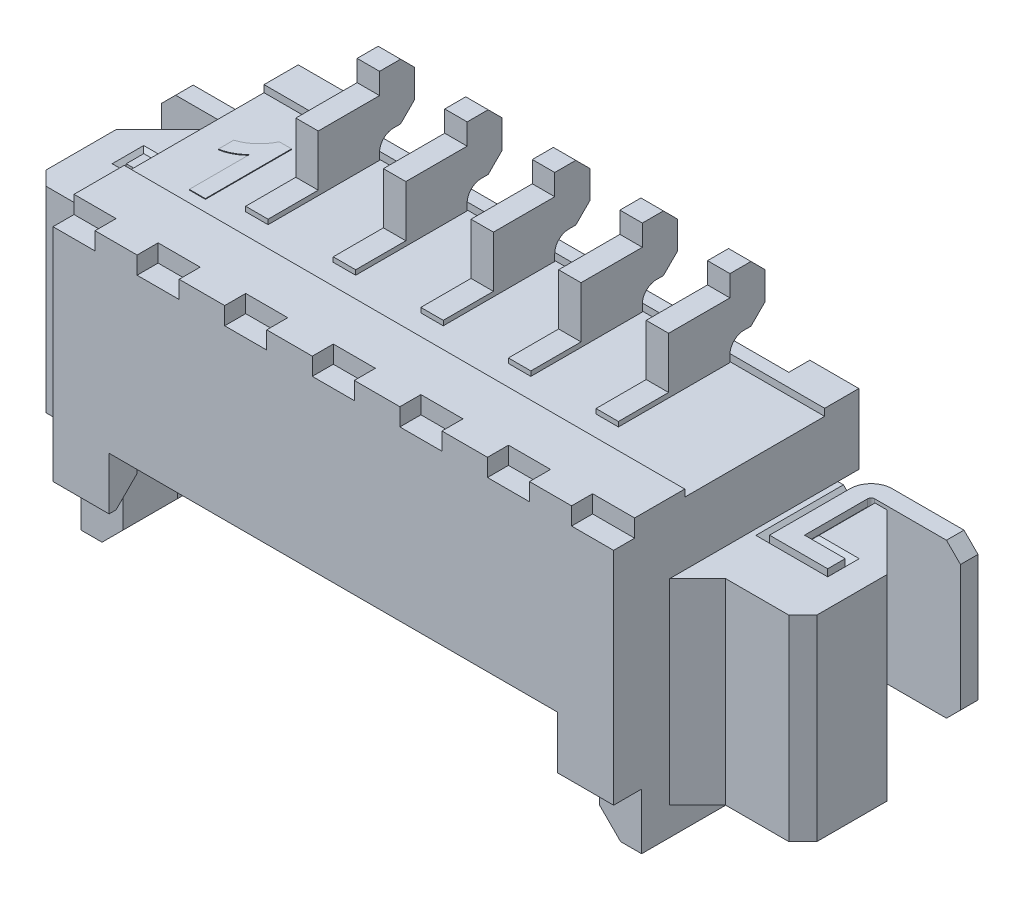
SolidWorks part; units mm, degrees
ref_plane "Спереди" through (0, 0, 0) normal (0, 0, 1) x (1, 0, 0)
ref_plane "Сверху" through (0, 0, 0) normal (0, 1, 0) x (1, 0, 0)
ref_plane "Справа" through (0, 0, 0) normal (1, 0, 0) x (0, 0, -1)
sketch "Эскиз1" plane through (0, 0, 0) normal (0, 1, 0) x (1, 0, 0)
  line L0 (3.4, -1.5) -> (3.4, -0.7)
  line L1 (-4, -0.3) -> (-4, -3.1)
  line L2 (3.7, -1.5) -> (3.4, -1.5)
  line L3 (-3.7, -2.325) -> (-3.7, -1.5)
  line L4 (-4, -3.1) -> (-3.4, -3.1)
  line L5 (-3.7, -2.325) -> (-3.4, -2.325)
  line L6 (-3.4, -2.325) -> (-3.4, -3.1)
  line L7 (3.4, -2.325) -> (3.4, -3.1)
  line L8 (3.7, -2.325) -> (3.4, -2.325)
  line L9 (0, -1.9) -> (0, -3.3692) construction
  line L10 (-3.7, -1.5) -> (-3.4, -1.5)
  line L11 (-3.4, -1.5) -> (-3.4, -0.7)
  line L12 (4, -3.1) -> (3.4, -3.1)
  line L13 (3.7, -2.325) -> (3.7, -1.5)
  line L14 (4, -0.3) -> (4, -3.1)
  line L15 (-4, -0.3) -> (4, -0.3)
  line L16 (3.4, -0.7) -> (-3.4, -0.7)
  dimension "D1" = 0.6
  dimension "D2" = 0.3
  dimension "D3" = 0.3
  dimension "D4" = 2.8
  dimension "D5" = 4
extrude "Вытянуть1" add sketch "Эскиз1" against normal blind 4.2
sketch "Эскиз2" plane through (0, 0, 0) normal (0, 1, 0) x (1, 0, 0)
  line L0 (-4, -3.1) -> (-3.4, -3.1)
  line L1 (-3.4, -3.1) -> (-3.4, -3.5)
  line L2 (-4, -3.1) -> (-4, -3.5)
  line L3 (-4, -3.5) -> (-3.4, -3.5)
  line L4 (0, -2.1744) -> (0, -2.7597) construction
  line L5 (4, -3.5) -> (3.4, -3.5)
  line L6 (4, -3.1) -> (4, -3.5)
  line L7 (3.4, -3.1) -> (3.4, -3.5)
  line L8 (4, -3.1) -> (3.4, -3.1)
extrude "Вытянуть2" add sketch "Эскиз2" against normal blind 3.4
sketch "Эскиз3" plane through (0, 0, 0) normal (0, 1, 0) x (1, 0, 0)
  line L0 (0, -2.5358) -> (0, -3.4442) construction
  line L1 (-3.4, -3.1) -> (-3.2, -3.1)
  line L2 (-3.4, -3.5) -> (-3.4, -2.325) construction
  line L3 (-3.2, -3.1) -> (-3.2, -3.5)
  line L4 (-3.2, -3.5) -> (-3.4, -3.5)
  line L5 (-3.4, -3.5) -> (-3.4, -3.1)
  line L6 (3.4, -3.5) -> (3.4, -3.1)
  line L7 (3.2, -3.5) -> (3.4, -3.5)
  line L8 (3.2, -3.1) -> (3.2, -3.5)
  line L9 (3.4, -3.1) -> (3.2, -3.1)
  dimension "D1" = 0.2
extrude "Вытянуть3" add sketch "Эскиз3" against normal blind 3.4
sketch "Эскиз5" plane through (0, 0, 0) normal (0, 1, 0) x (1, 0, 0)
  line L0 (-3.2, -3.1) -> (-3.2, -3.5)
  line L1 (3.2, -3.1) -> (3.2, -3.5)
  line L2 (3.2, -3.5) -> (-3.2, -3.5)
  line L3 (-3.2, -3.1) -> (3.2, -3.1)
extrude "Вытянуть4" add sketch "Эскиз5" against normal blind 2.65
chamfer "Фаска1" distance 0.3 angle 45 8 edges at (0, -2.65, 3.1) (3.3, -3.4, 3.1) (-3.3, -3.4, 3.1) (3.4, -4.2, 2.7125) (3.4, -4.2, 1.1) (0, -4.2, 0.7) (-3.4, -4.2, 1.1) (-3.4, -4.2, 2.7125)
sketch "Эскиз6" plane through (0, 0, 0) normal (0, 0, 1) x (1, 0, 0)
  line L0 (0, -1.2805) -> (0, -2.2251) construction
  line L1 (-2.5, -1.55) -> (-1.25, -1.55)
  line L2 (-1.25, -1.55) -> (-1.25, -2.7)
  line L3 (-2.5, -2.7) -> (-2.035, -2.7)
  line L4 (-2.5, -2.7) -> (-2.5, -1.55)
  line L5 (-4, -3.4) -> (-4, 0) construction
  line L6 (1.715, -4.5729) -> (1.715, -2.7)
  line L7 (2.035, -4.5729) -> (1.715, -4.5729)
  line L8 (2.035, -2.7) -> (2.035, -4.5729)
  line L9 (1.25, -2.7) -> (1.715, -2.7)
  line L10 (-1.25, -2.7) -> (-1.715, -2.7)
  line L11 (-2.035, -2.7) -> (-2.035, -4.5729)
  line L12 (-2.035, -4.5729) -> (-1.715, -4.5729)
  line L13 (-1.715, -4.5729) -> (-1.715, -2.7)
  line L14 (2.5, -2.7) -> (2.5, -1.55)
  line L15 (2.5, -2.7) -> (2.035, -2.7)
  line L16 (1.25, -1.55) -> (1.25, -2.7)
  line L17 (2.5, -1.55) -> (1.25, -1.55)
  dimension "D1" = 1.25
  dimension "D2" = 1.5
  dimension "D3" = 0.465
  dimension "D4" = 0.465
extrude "Вытянуть5" cut sketch "Эскиз6" along normal blind 0.6 from offset 0.2
sketch "Эскиз7" [suppressed] plane through (0, 0, 0) normal (0, 0, 1) x (1, 0, 0)
  line L0 (-0.16, -2.7) -> (-0.625, -2.7)
  line L1 (0.625, -2.7) -> (0.625, -1.55)
  line L2 (0.625, -1.55) -> (-0.625, -1.55)
  line L3 (-0.625, -1.55) -> (-0.625, -2.7)
  line L4 (-0.16, -2.7) -> (-0.16, -4.3)
  line L5 (0.16, -2.7) -> (0.16, -4.3)
  line L6 (0.16, -2.7) -> (0.625, -2.7)
  line L7 (0.16, -4.3) -> (-0.16, -4.3)
extrude "Вытянуть6" [suppressed] cut sketch "Эскиз7" along normal blind 0.6 from offset 0.2
sketch "Эскиз8" plane through (0, 0, 0) normal (0, 1, 0) x (1, 0, 0)
  line L0 (-4, -3.5) -> (-4, -0.3)
  line L1 (-4, -0.3) -> (-4, -3.5) construction
  line L2 (4, -3.5) -> (4, -0.3)
  line L3 (4, -3.5) -> (4, -0.3) construction
  line L4 (-4, -0.3) -> (4, -0.3)
  line L5 (4, -3.5) -> (-4, -3.5)
extrude "Вытянуть7" add sketch "Эскиз8" against normal blind 1.3
sketch "Эскиз9" plane through (0, 0, 0) normal (0, 0, 1) x (1, 0, 0)
  line L0 (0, -1.6402) -> (0, 1.5884) construction
  line L1 (-4, 0) -> (-3.3, 0)
  line L2 (-4, 0) -> (4, 0) construction
  line L3 (-3.3, 0) -> (-3.3, -1)
  line L4 (-4, 0) -> (-4, -1)
  line L5 (-4, -3.4) -> (-4, 0) construction
  line L6 (-4, -1) -> (-3.3, -1)
  line L7 (4, -1) -> (3.3, -1)
  line L8 (4, 0) -> (4, -1)
  line L9 (3.3, 0) -> (3.3, -1)
  line L10 (4, 0) -> (3.3, 0)
  line L11 (-3.3, -2.9) -> (-3.3, -4.2)
  line L12 (3.7, -4.2) -> (2.035, -4.2) construction
  line L13 (-3.3, -4.2) -> (-4, -4.2)
  line L14 (-4, -4.2) -> (-4, -2.9)
  line L15 (-4, -2.9) -> (-3.3, -2.9)
  line L16 (4, -2.9) -> (3.3, -2.9)
  line L17 (4, -4.2) -> (4, -2.9)
  line L18 (3.3, -4.2) -> (4, -4.2)
  line L19 (3.3, -2.9) -> (3.3, -4.2)
  dimension "D1" = 0.7
extrude "Вытянуть8" add sketch "Эскиз9" along normal blind 0.3
sketch "Эскиз11" plane through (0, 0, 0) normal (0, 1, 0) x (1, 0, 0)
  line L0 (-0.16, -1.075) -> (0.16, -1.075)
  line L1 (0.16, -1.075) -> (0.16, -1.775)
  line L2 (0.16, -1.775) -> (-0.16, -1.775)
  line L3 (-0.16, -1.775) -> (-0.16, -1.075)
  line L4 (0, -0.51) -> (0, -0.8079) construction
  dimension "D1" = 0.32
  dimension "D2" = 0.16
extrude "Вытянуть10" add sketch "Эскиз11" along normal blind 3 and the other way blind 0.25 draft 25 from offset 3.3 offset against normal yes
sketch "Эскиз16" plane through (0, 0, 0) normal (0, 1, 0) x (1, 0, 0)
  line L0 (0, -2.2797) -> (0, -3.0653) construction
  line L1 (-0.3, -3.2) -> (0.3, -3.2)
  line L2 (0.3, -3.2) -> (0.3, -3.5)
  line L3 (0.3, -3.5) -> (-0.3, -3.5)
  line L4 (-0.3, -3.5) -> (-0.3, -3.2)
  dimension "D1" = 0.6
  dimension "D2" = 0.3
extrude "Вытянуть15" cut sketch "Эскиз16" against normal blind 0.25
sketch "Эскиз17" plane through (0, 0, 0) normal (0, 1, 0) x (1, 0, 0)
  line L0 (0, -1.6063) -> (0, -2.1824)
  line L1 (3.4, -3.2) -> (4, -3.2)
  line L2 (4, -3.2) -> (4, -3.5)
  line L3 (4, -3.5) -> (3.4, -3.5)
  line L4 (3.4, -3.5) -> (3.4, -3.2)
  line L5 (4, -3.5) -> (4, 0) construction
  line L6 (-3.4, -3.5) -> (-3.4, -3.2)
  line L7 (-4, -3.5) -> (-3.4, -3.5)
  line L8 (-4, -3.2) -> (-4, -3.5)
  line L9 (-3.4, -3.2) -> (-4, -3.2)
  dimension "D1" = 0.6
  dimension "D2" = 0.6
extrude "Вытянуть16" cut sketch "Эскиз17" against normal blind 0.25 contours L4 L3 L2 L1 | L6 L9 L8 L7 region at (3.7, 0, 3.35) region at (-3.7, 0, 3.35)
sketch "Эскиз19" plane through (0, 0, 0) normal (0, 1, 0) x (1, 0, 0)
  line L0 (-3.1, -2.2255) -> (-3.1, -0.9961)
  line L1 (-3.1, -0.9961) -> (-3.2746, -0.9961)
  line L2 (-3.1, -2.2255) -> (-3.329, -2.2255)
  line L3 (-3.329, -2.2255) -> (-3.329, -1.3668)
  line L4 (-3.6197, -1.3027) -> (-3.6197, -1.5216)
  line L5 (-4, 0) -> (-4, -3.2) construction
  arc A0 (-3.6197, -1.3027) -> (-3.2746, -0.9961) centre (-3.8055, -0.7461) ccw
  arc A1 (-3.329, -1.3668) -> (-3.6197, -1.5216) centre (-3.7219, -0.9794) cw
  dimension "D1" = 0.229
  dimension "D2" = 0.8587
  dimension "D3" = 0.2907
  dimension "D4" = 1.2293
  dimension "D5" = 0.1746
  dimension "D6" = 0.4473
  dimension "D7" = 0.4765
  dimension "D8" = 0.2189
  dimension "D9" = 0.9
sketch "Эскиз22" plane through (0.16, 0, 0) normal (1, 0, 0) x (0, 0, -1)
  line L0 (-1.375, 0.7) -> (-1.375, -0.0318)
  line L1 (-0.5, 1) -> (-0.5, 0.7)
  line L2 (-0.5, 1) -> (-0.2, 1)
  line L3 (0, 0.8) -> (0, 0.4)
  line L4 (-0.2, 0.2) -> (-0.3, 0.2)
  line L5 (-0.5, 0.7) -> (-1.375, 0.7)
  line L6 (-1.375, -0.2) -> (-0.5, -0.2)
  line L7 (-0.5, -0.2) -> (-0.5, 0)
  line L8 (-0.2, 1) -> (0, 0.8)
  line L9 (0, 0.4) -> (-0.2, 0.2)
  line L10 (-1.375, -0.0318) -> (-2.091, -0.0318)
  line L11 (-2.091, -0.0318) -> (-2.091, -0.2)
  line L12 (-2.091, -0.2) -> (-1.375, -0.2)
  arc A0 (-0.3, 0.2) -> (-0.5, 0) centre (-0.3, 0) ccw
  point P5 (0, 1)
  point P6 (0, 0.2)
  dimension "D1" = 0.2
sketch "Эскиз24" plane through (0, 0, 0) normal (0, 1, 0) x (1, 0, 0)
  line L0 (0, -1.766) -> (0, -2.4846) construction
  line L1 (-4, -0.4884) -> (-4, -2.4846)
  line L2 (-4, 0) -> (-4, -3.2) construction
  line L3 (4, -0.4884) -> (4, -2.4846)
  line L4 (-4, -0.4884) -> (4, -0.4884)
  line L5 (4, -2.4846) -> (-4, -2.4846)
extrude "Вытянуть28" cut sketch "Эскиз24" against normal blind 0.1
extrude "Вытянуть29" add sketch "Эскиз19" along normal blind 0.01 from offset 0.1 offset against normal yes
extrude "Вытянуть30" add sketch "Эскиз22" against normal blind 0.32
pattern_linear "Линейный массив1" count 3 spacing 1.25 along (1, 0, 0) count 3 spacing 1.25 along (-1, 0, 0) of "Вытянуть15"
pattern_linear "Линейный массив17" count 3 spacing 1.25 along (-1, 0, 0) count 3 spacing 1.25 along (1, 0, 0) of "Вытянуть10", "Вытянуть30"
sketch "Эскиз26" plane through (0, 0, 0) normal (0, 1, 0) x (1, 0, 0)
  line L0 (-5.5, -1.1) -> (-5.5, -2.1)
  line L1 (-4, -0.4884) -> (-4, -2.4846) construction
  line L2 (-4, -0.3) -> (-4.7, -0.3)
  line L3 (-4, -0.3) -> (-4, -2.7)
  line L4 (0, -0.0818) -> (0, -1.0086) construction
  line L5 (-4, 0) -> (-4, -3.1) construction
  line L6 (-5.3, -2.3) -> (-4.4, -2.3)
  line L7 (-4.4, -2.3) -> (-4, -2.7)
  line L8 (-4.7, -0.3) -> (-5.5, -1.1)
  line L9 (-5.5, -2.1) -> (-5.3, -2.3)
  line L10 (5.5, -2.1) -> (5.3, -2.3)
  line L11 (4.7, -0.3) -> (5.5, -1.1)
  line L12 (4.4, -2.3) -> (4, -2.7)
  line L13 (5.3, -2.3) -> (4.4, -2.3)
  line L14 (4, -0.3) -> (4, -2.7)
  line L15 (4, -0.3) -> (4.7, -0.3)
  line L16 (5.5, -1.1) -> (5.5, -2.1)
  point P13 (-5.5, -0.3)
  point P15 (-5.5, -2.3)
  point P24 (5.5, -2.3)
  point P25 (5.5, -0.3)
  dimension "D1" = 1.5
  dimension "D2" = 0.4
extrude "Вытянуть31" add sketch "Эскиз26" against normal blind 2.8 from offset 1 offset against normal yes
sketch "Эскиз27" plane through (0, 0, 0) normal (0, 1, 0) x (1, 0, 0)
  line L0 (-4.18, -0.2231) -> (-4.18, -1.45)
  line L1 (-4.18, -1.45) -> (-5.0058, -1.45)
  line L2 (-5.0058, -1.45) -> (-5.0058, -1.2)
  line L3 (-5.0058, -1.2) -> (-4.43, -1.2)
  line L4 (-4.43, -1.2) -> (-4.43, -0.2231)
  line L5 (-4.43, -0.2231) -> (-4.18, -0.2231)
  line L6 (0, 0.061) -> (0, -0.7665) construction
  line L7 (-4, -2.7) -> (-4, -0.3) construction
  line L8 (4.43, -0.2231) -> (4.18, -0.2231)
  line L9 (4.43, -1.2) -> (4.43, -0.2231)
  line L10 (5.0058, -1.2) -> (4.43, -1.2)
  line L11 (5.0058, -1.45) -> (5.0058, -1.2)
  line L12 (4.18, -1.45) -> (5.0058, -1.45)
  line L13 (4.18, -0.2231) -> (4.18, -1.45)
  dimension "D1" = 0.18
  dimension "D2" = 0.25
  dimension "D3" = 0.8258
extrude "Вытянуть32" cut sketch "Эскиз27" along normal blind 0.11 draft 45 from offset 1.1 draft outward yes offset against normal yes
sketch "Эскиз28" plane through (0, 0, 0) normal (0, 1, 0) x (1, 0, 0)
  line L0 (-5.7, 0) -> (-4.475, 0)
  line L1 (-4.175, -0.3) -> (-4.175, -1.45)
  line L2 (-4.175, -1.45) -> (-5.005, -1.45)
  line L3 (-5.005, -1.45) -> (-5.005, -1.2)
  line L4 (-5.005, -1.2) -> (-4.425, -1.2)
  line L5 (-4.425, -1.2) -> (-4.425, -0.3)
  line L6 (-4.475, -0.25) -> (-5.7, -0.25)
  line L7 (-5.7, -0.25) -> (-5.7, 0)
  line L8 (-4, -0.4884) -> (-4, -2.4846) construction
  line L9 (0, 0.2762) -> (0, -0.1789) construction
  line L10 (5.7, -0.25) -> (5.7, 0)
  line L11 (4.475, -0.25) -> (5.7, -0.25)
  line L12 (4.425, -1.2) -> (4.425, -0.3)
  line L13 (5.005, -1.2) -> (4.425, -1.2)
  line L14 (5.005, -1.45) -> (5.005, -1.2)
  line L15 (4.175, -1.45) -> (5.005, -1.45)
  line L16 (4.175, -0.3) -> (4.175, -1.45)
  line L17 (5.7, 0) -> (4.475, 0)
  arc A0 (-4.475, 0) -> (-4.175, -0.3) centre (-4.475, -0.3) cw
  arc A1 (-4.425, -0.3) -> (-4.475, -0.25) centre (-4.475, -0.3) ccw
  arc A2 (4.425, -0.3) -> (4.475, -0.25) centre (4.475, -0.3) cw
  arc A3 (4.475, 0) -> (4.175, -0.3) centre (4.475, -0.3) ccw
  dimension "D1" = 0.3
  dimension "D2" = 0.05
  dimension "D3" = 0.175
  dimension "D4" = 0.25
  dimension "D5" = 1.275
  dimension "D6" = 0.58
extrude "Вытянуть33" add sketch "Эскиз28" against normal blind 2.2 from offset 1 offset against normal yes
chamfer "Фаска2" distance 0.2 angle 45 4 edges at (5.7, -1, 0.125) (5.7, -3.2, 0.125) (-5.7, -1, 0.125) (-5.7, -3.2, 0.125)
